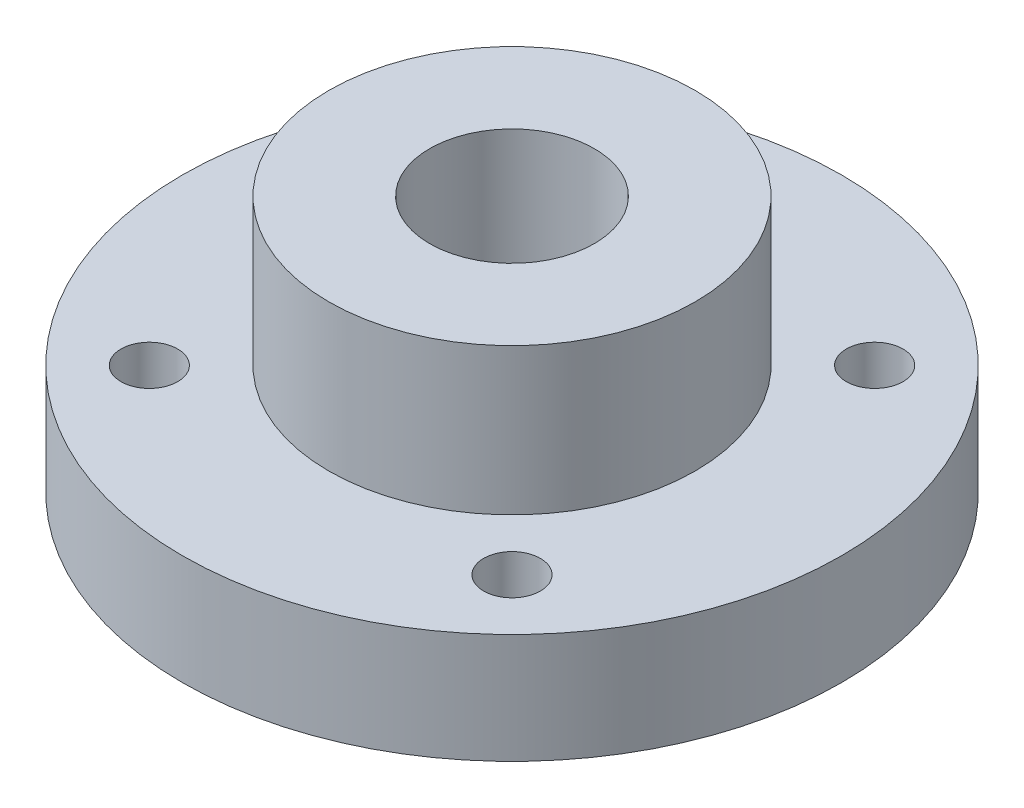
SolidWorks part; units mm, degrees
material "6061-T6 (SS)"
ref_plane "Front Plane" through (0, 0, 0) normal (0, 0, 1) x (1, 0, 0)
ref_plane "Top Plane" through (0, 0, 0) normal (0, 1, 0) x (1, 0, 0)
ref_plane "Right Plane" through (0, 0, 0) normal (1, 0, 0) x (0, 0, -1)
sketch "Sketch1" plane through (0, 0, 0) normal (0, 0, 1) x (1, 0, 0)
  line L0 (0, 0) -> (0, -14.566) construction
  line L6 (-11.1125, -70.6552) -> (-11.1125, -77.0052)
  line L7 (-15.875, -51.6052) -> (-15.875, -64.3052)
  line L8 (-15.875, -64.3052) -> (-28.575, -64.3052)
  line L9 (-28.575, -64.3052) -> (-28.575, -73.8302)
  line L12 (76.2, -73.8302) -> (-76.2, -73.8302) construction
  line L14 (-14.2875, -73.8302) -> (-14.2875, -77.0052)
  line L15 (-14.2875, -77.0052) -> (-11.1125, -77.0052)
  line L17 (-28.575, -73.8302) -> (-19.05, -73.8302)
  line L18 (-19.05, -73.8302) -> (-19.05, -70.6933)
  line L19 (-19.05, -70.6933) -> (-14.2875, -70.6933)
  line L20 (-14.2875, -70.6933) -> (-14.2875, -73.8302)
  line L21 (-15.875, -51.6052) -> (-4.7625, -51.6052)
  line L22 (-4.7625, -51.6052) -> (-4.7625, -70.6552)
  line L23 (-4.7625, -70.6552) -> (-11.1125, -70.6552)
  dimension "D2" = 3.175
  dimension "D3" = 9.525
  dimension "D4" = 9.525
  dimension "D5" = 6.35
  dimension "D6" = 12.7
  dimension "D7" = 57.15
  dimension "D8" = 19.05
  dimension "D9" = 28.575
  dimension "D11" = 3.175
  dimension "D12" = 38.1
  dimension "D13" = 3.1369
revolve "Revolve1" add sketch "Sketch1" angle 360 about L0
hole_wizard "#10 (0.1935) Diameter Hole1" positions "Sketch2" profile "Sketch3" hole size "#10" standard "ANSI Inch" end condition through all
sketch "Sketch2" plane through (0, -51.6052, 0) normal (0, 1, 0) x (1, 0, 0)
  line L0 (-15.7154, 15.7154) -> (15.7154, -15.7154) construction
  line L2 (15.7154, 15.7154) -> (-15.7154, -15.7154) construction
  line L3 (0, 0) -> (-24.6236, 0) construction
  point P0 (15.7154, 15.7154)
  point P2 (-15.7154, 15.7154)
  point P4 (-15.7154, -15.7154)
  point P6 (15.7154, -15.7154)
  dimension "D1" = 44.45
  dimension "D2" = 45
sketch "Sketch3" plane through (15.7154, -51.6052, -15.7154) normal (1, 0, 0) x (0, 0, 1)
  line L0 (0, 0) -> (0, 25.4)
  line L1 (0, 25.4) -> (2.4574, 25.4)
  line L2 (2.4574, 25.4) -> (2.4574, 0)
  line L5 (2.4574, 0) -> (0, 0)
  line L11 (0, -6.35) -> (0, 107.95) construction
  dimension "Thru Hole Dia." = 4.9149
  dimension "Thru Hole Depth" = 25.4
hole_wizard "Pipe Tap Drill for 3/8 Tap1" positions "3DSketch1" profile "Sketch4" hole size "3/8" standard "ANSI Inch"
sketch3d "3DSketch1"
  circle A1 centre (0, -51.6052, 0) radius 15.875 construction
  point P0 (0, -51.6052, 0)
  point P9 (0, -35.7302, 0)
sketch "Sketch4" plane through (0, -51.6052, 0) normal (1, 0, 0) x (0, 0, 1)
  line L0 (0, 0) -> (0, 16.9886)
  line L1 (0, 16.9886) -> (7.1374, 12.7)
  line L2 (7.1374, 12.7) -> (7.1374, 0)
  line L5 (7.1374, 0) -> (0, 0)
  line L10 (0, 16.9886) -> (-7.1374, 12.7) construction
  line L11 (0, -6.35) -> (0, 107.95) construction
  dimension "Hole Dia." = 14.2748
  dimension "Hole Depth" = 12.7
  dimension "Drill Angle" = 118
